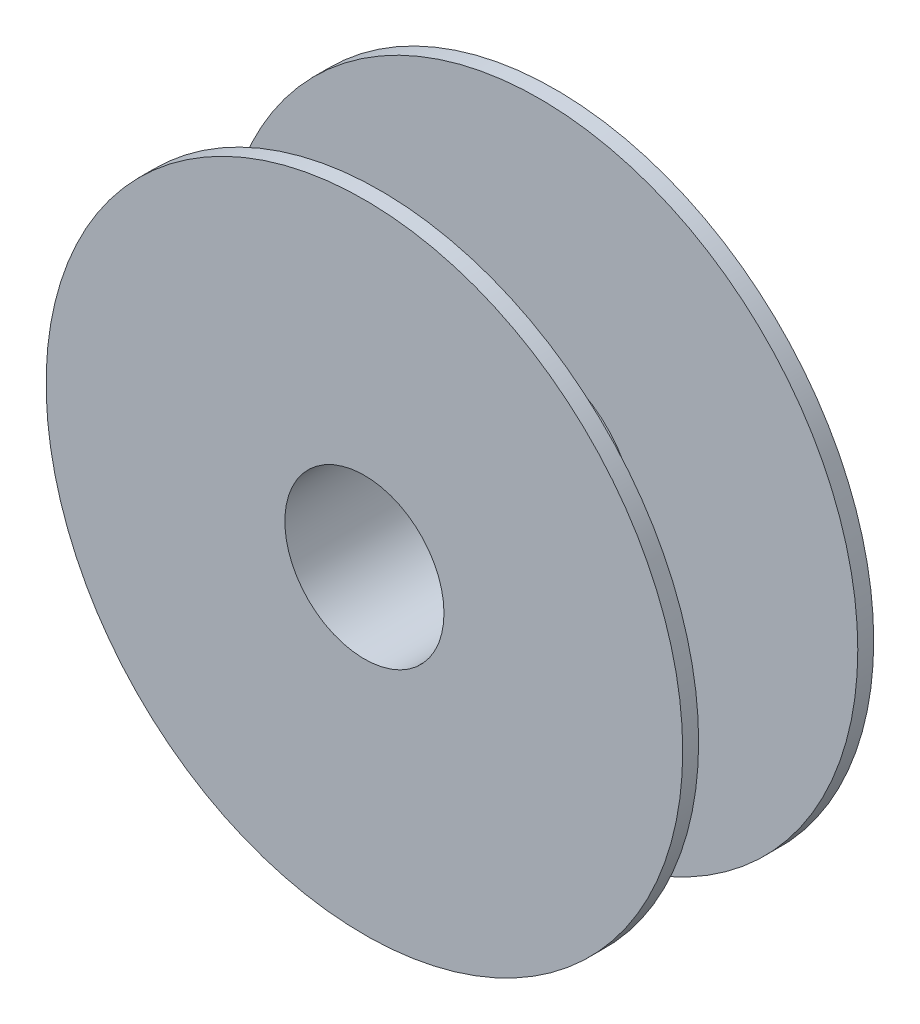
SolidWorks part; units mm, degrees
ref_plane "Front Plane" through (0, 0, 0) normal (0, 0, 1) x (1, 0, 0)
ref_plane "Top Plane" through (0, 0, 0) normal (0, 1, 0) x (1, 0, 0)
ref_plane "Right Plane" through (0, 0, 0) normal (1, 0, 0) x (0, 0, -1)
sketch "Sketch1" plane through (0, 0, 0) normal (0, 0, 1) x (1, 0, 0)
  circle A0 centre (0, 0) radius 100
  circle A1 centre (0, 0) radius 25
  dimension "D1" = 50
  dimension "D2" = 200
extrude "Boss-Extrude1" add sketch "Sketch1" along normal blind 60
shell "Shell1" thickness 5 removed face at (100, 0, 60)
